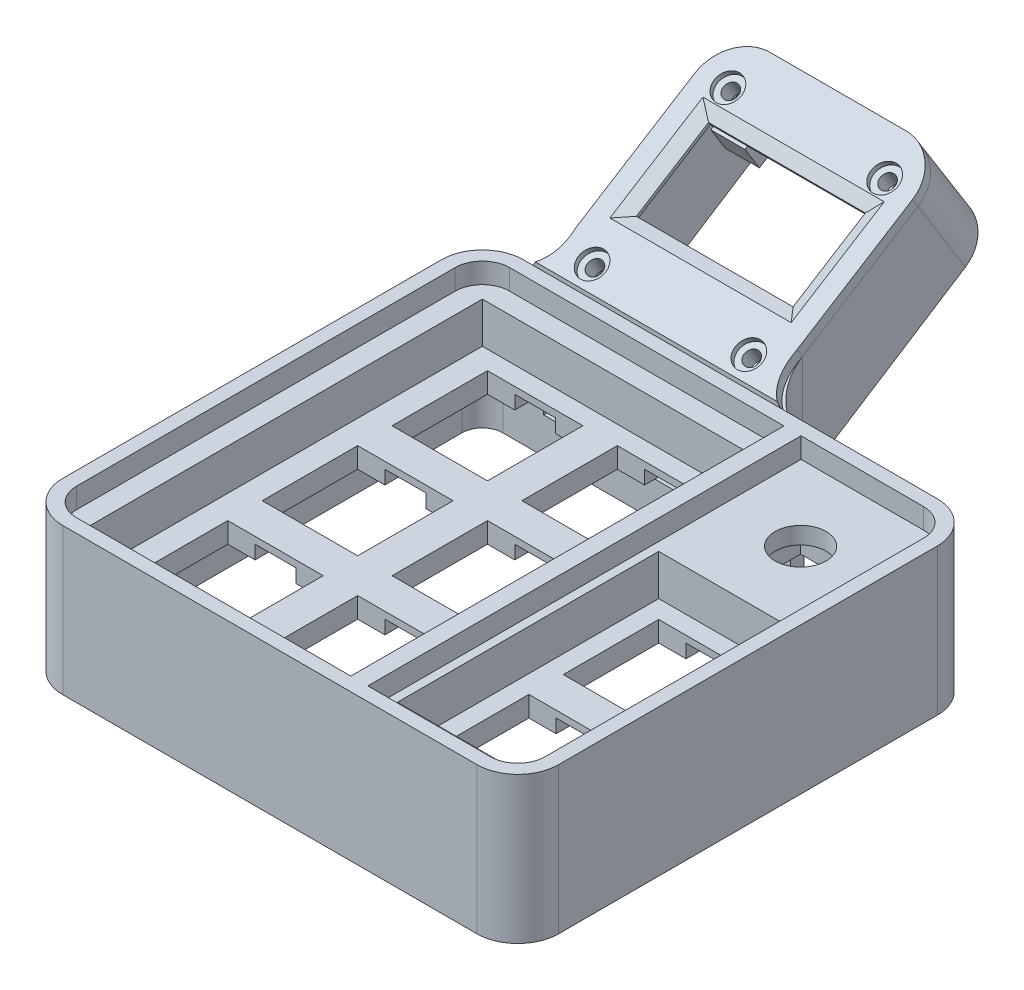
SolidWorks part; units mm, degrees
ref_plane "Ebene vorne" through (0, 0, 0) normal (0, 0, 1) x (1, 0, 0)
ref_plane "Ebene oben" through (0, 0, 0) normal (0, 1, 0) x (1, 0, 0)
ref_plane "Ebene rechts" through (0, 0, 0) normal (1, 0, 0) x (0, 0, -1)
sketch "Skizze1" plane through (0, 0, 0) normal (0, 1, 0) x (1, 0, 0)
  line L0 (-33.9289, -4.0378) -> (-33.9289, -11.968) construction
  line L1 (-59.9789, 36.498) -> (-45.9789, 36.498)
  line L2 (-59.9789, 36.498) -> (-59.9789, 22.498)
  line L3 (-59.9789, 22.498) -> (-45.9789, 22.498)
  line L4 (-45.9789, 36.498) -> (-45.9789, 22.498)
  line L5 (-40.9289, 36.498) -> (-26.9289, 36.498)
  line L6 (-40.9289, 36.498) -> (-40.9289, 22.498)
  line L7 (-40.9289, 22.498) -> (-26.9289, 22.498)
  line L8 (-26.9289, 36.498) -> (-26.9289, 22.498)
  line L9 (-59.9789, 17.448) -> (-45.9789, 17.448)
  line L10 (-59.9789, 17.448) -> (-59.9789, 3.448)
  line L11 (-59.9789, 3.448) -> (-45.9789, 3.448)
  line L12 (-45.9789, 17.448) -> (-45.9789, 3.448)
  line L13 (-40.9289, 17.448) -> (-26.9289, 17.448)
  line L14 (-40.9289, 17.448) -> (-40.9289, 3.448)
  line L15 (-40.9289, 3.448) -> (-26.9289, 3.448)
  line L16 (-26.9289, 17.448) -> (-26.9289, 3.448)
  line L17 (-15.8039, 3.448) -> (-1.8039, 3.448)
  line L18 (-15.8039, 3.448) -> (-15.8039, 17.448)
  line L19 (-15.8039, 17.448) -> (-1.8039, 17.448)
  line L20 (-1.8039, 3.448) -> (-1.8039, 17.448)
  line L21 (-59.9789, -15.602) -> (-45.9789, -15.602)
  line L22 (-59.9789, -15.602) -> (-59.9789, -1.602)
  line L23 (-59.9789, -1.602) -> (-45.9789, -1.602)
  line L24 (-45.9789, -15.602) -> (-45.9789, -1.602)
  line L25 (-40.9289, -15.602) -> (-26.9289, -15.602)
  line L26 (-40.9289, -15.602) -> (-40.9289, -1.602)
  line L27 (-40.9289, -1.602) -> (-26.9289, -1.602)
  line L28 (-26.9289, -15.602) -> (-26.9289, -1.602)
  line L29 (-15.8039, -15.602) -> (-1.8039, -15.602)
  line L30 (-15.8039, -15.602) -> (-15.8039, -1.602)
  line L31 (-15.8039, -1.602) -> (-1.8039, -1.602)
  line L32 (-1.8039, -15.602) -> (-1.8039, -1.602)
  line L33 (-68.4539, 44.223) -> (4.2961, 44.223)
  line L34 (-68.4539, 44.223) -> (-68.4539, -23.332)
  line L35 (-68.4539, -23.332) -> (4.2961, -23.332)
  line L36 (4.2961, 44.223) -> (4.2961, -23.332)
  line L37 (-8.8039, -2.5984) -> (-8.8039, -10.451) construction
  line L38 (-52.9789, -1.8609) -> (-52.9789, -10.0378) construction
  dimension "D1" = 14
  dimension "D2" = 14
  dimension "D3" = 5.05
  dimension "D4" = 5.05
  dimension "D5" = 5.05
  dimension "D6" = 11.125
  dimension "D7" = 7.725
  dimension "D8" = 8.475
  dimension "D9" = 7.73
  dimension "D10" = 6.1
extrude "Aufsatz-Linear austragen1" add sketch "Skizze1" along normal blind 3
sketch "Skizze2" plane through (0, 3, 0) normal (0, 1, 0) x (1, 0, 0)
  line L1 (-68.4539, 44.223) -> (4.2961, 44.223)
  line L2 (-68.4539, 44.223) -> (-68.4539, -23.332)
  line L3 (-68.4539, -23.332) -> (4.2961, -23.332)
  line L4 (4.2961, 44.223) -> (4.2961, -23.332)
  line L5 (-66.4539, 42.223) -> (2.2961, 42.223)
  line L6 (-66.4539, 42.223) -> (-66.4539, -21.332)
  line L7 (-66.4539, -21.332) -> (2.2961, -21.332)
  line L8 (2.2961, 42.223) -> (2.2961, -21.332)
  dimension "D1" = 2
  dimension "D2" = 2
  dimension "D3" = 2
  dimension "D4" = 2
extrude "Aufsatz-Linear austragen2" add sketch "Skizze2" along normal blind 9
sketch "Skizze3" plane through (0, 3, 0) normal (0, 1, 0) x (1, 0, 0)
  line L0 (2.2961, 42.223) -> (-66.4539, 42.223) construction
  line L1 (-22.2039, 42.223) -> (-19.7039, 42.223)
  line L2 (-22.2039, 42.223) -> (-22.2039, -21.332)
  line L3 (-22.2039, -21.332) -> (-19.7039, -21.332)
  line L4 (-19.7039, 42.223) -> (-19.7039, -21.332)
  line L5 (-66.4539, -21.332) -> (2.2961, -21.332) construction
  line L6 (4.2961, -23.332) -> (4.2961, 44.223) construction
  dimension "D1" = 2.5
  dimension "D2" = 24
extrude "Aufsatz-Linear austragen3" add sketch "Skizze3" along normal up to surface (9 mm away) up to face at (-32.0789, 12, -10.4455)
sketch "Skizze4" plane through (0, 3, 0) normal (0, 1, 0) x (1, 0, 0)
  line L0 (-22.2039, 42.223) -> (-22.2039, -21.332) construction
  line L1 (-63.4539, 39.223) -> (-23.4539, 39.223)
  line L2 (-63.4539, 39.223) -> (-63.4539, -18.332)
  line L3 (-63.4539, -18.332) -> (-23.4539, -18.332)
  line L4 (-23.4539, 39.223) -> (-23.4539, -18.332)
  line L5 (-68.4539, -23.332) -> (4.2961, -23.332) construction
  line L6 (-68.4539, 44.223) -> (-68.4539, -23.332) construction
  line L7 (4.2961, 44.223) -> (-68.4539, 44.223) construction
  line L9 (-66.4539, 42.223) -> (-22.2039, 42.223)
  line L10 (-66.4539, 42.223) -> (-66.4539, -21.332)
  line L11 (-66.4539, -21.332) -> (-22.2039, -21.332)
  line L12 (-22.2039, 42.223) -> (-22.2039, -21.332)
  dimension "D1" = 1.25
  dimension "D2" = 5
  dimension "D3" = 5
  dimension "D4" = 5
extrude "Aufsatz-Linear austragen4" add sketch "Skizze4" along normal offset from surface (6 mm away) 3 up to face at (-8.7039, 12, -10.4455)
sketch "Skizze5" plane through (0, 3, 0) normal (0, 1, 0) x (1, 0, 0)
  line L0 (-1.8039, 17.448) -> (-15.8039, 17.448) construction
  line L1 (-18.4539, 20.098) -> (0.8461, 20.098)
  line L2 (-18.4539, 20.098) -> (-18.4539, -18.252)
  line L3 (-18.4539, -18.252) -> (0.8461, -18.252)
  line L4 (0.8461, 20.098) -> (0.8461, -18.252)
  line L5 (-1.8039, 3.448) -> (-1.8039, 17.448) construction
  line L6 (-15.8039, -15.602) -> (-1.8039, -15.602) construction
  line L7 (-15.8039, -1.602) -> (-15.8039, -15.602) construction
  line L9 (-19.7039, 42.223) -> (2.2961, 42.223)
  line L10 (-19.7039, 42.223) -> (-19.7039, -21.332)
  line L11 (-19.7039, -21.332) -> (2.2961, -21.332)
  line L12 (2.2961, 42.223) -> (2.2961, -21.332)
  dimension "D1" = 2.65
  dimension "D2" = 2.65
  dimension "D3" = 2.65
  dimension "D4" = 2.65
extrude "Aufsatz-Linear austragen5" add sketch "Skizze5" along normal offset from surface (6 mm away) 3 up to face at (-8.7039, 12, -10.4455)
sketch "Skizze6" plane through (0, 9, 0) normal (0, 1, 0) x (1, 0, 0)
  line L1 (-8.7039, 37.1976) -> (-8.7039, 23.8687) construction
  line L2 (-19.7039, -21.332) -> (-19.7039, 42.223) construction
  line L3 (2.2961, -21.332) -> (2.2961, 42.223) construction
  line L4 (-14.7078, 31.1605) -> (-1.2358, 31.1605) construction
  line L5 (2.2961, 42.223) -> (-19.7039, 42.223) construction
  line L6 (0.8461, 20.098) -> (-18.4539, 20.098) construction
  circle A0 centre (-8.7039, 31.1605) radius 3.75
  dimension "D1" = 7.5
extrude "Schnitt-Linear austragen1" cut sketch "Skizze6" against normal through all
sketch "Skizze7" plane through (0, 0, 0) normal (0, -1, 0) x (1, 0, 0)
  line L0 (-8.7039, -31.1605) -> (-8.7039, -37.2605) construction
  line L1 (-16.7039, -23.1605) -> (-0.7039, -23.1605)
  line L2 (-16.7039, -23.1605) -> (-16.7039, -39.1605)
  line L3 (-16.7039, -39.1605) -> (-0.7039, -39.1605)
  line L4 (-0.7039, -23.1605) -> (-0.7039, -39.1605)
  line L5 (-11.6454, -31.1605) -> (-3.5978, -31.1605) construction
  dimension "D1" = 16
  dimension "D2" = 16
extrude "Schnitt-Linear austragen2" cut sketch "Skizze7" against normal offset from surface (6.5 mm away) 2.5 up to face at (-8.7039, 9, -27.4105)
sketch "Skizze8" plane through (0, 0, 0) normal (0, -1, 0) x (1, 0, 0)
  line L1 (-68.4539, 23.332) -> (4.2961, 23.332)
  line L2 (-68.4539, 23.332) -> (-68.4539, -44.223)
  line L3 (-68.4539, -44.223) -> (4.2961, -44.223)
  line L4 (4.2961, 23.332) -> (4.2961, -44.223)
  line L5 (2.2961, -42.223) -> (-66.4539, -42.223)
  line L6 (2.2961, -42.223) -> (2.2961, 21.332)
  line L7 (2.2961, 21.332) -> (-66.4539, 21.332)
  line L8 (-66.4539, -42.223) -> (-66.4539, 21.332)
  dimension "D1" = 2
  dimension "D2" = 2
  dimension "D3" = 2
  dimension "D4" = 2
extrude "Aufsatz-Linear austragen6" add sketch "Skizze8" along normal blind 9.5
sketch "Skizze14" plane through (0, 0, 0) normal (0, -1, 0) x (1, 0, 0)
  line L0 (-52.9789, 16.4952) -> (-52.9789, -37.7006) construction
  line L1 (-55.9789, 17.602) -> (-49.9789, 17.602)
  line L2 (-55.9789, 17.602) -> (-55.9789, -38.498)
  line L3 (-55.9789, -38.498) -> (-49.9789, -38.498)
  line L4 (-49.9789, 17.602) -> (-49.9789, -38.498)
  line L5 (-36.9289, -38.498) -> (-30.9289, -38.498)
  line L6 (-36.9289, -38.498) -> (-36.9289, 17.602)
  line L7 (-36.9289, 17.602) -> (-30.9289, 17.602)
  line L8 (-30.9289, -38.498) -> (-30.9289, 17.602)
  line L9 (-11.8039, 17.602) -> (-5.8039, 17.602)
  line L10 (-11.8039, 17.602) -> (-11.8039, -19.448)
  line L11 (-11.8039, -19.448) -> (-5.8039, -19.448)
  line L12 (-5.8039, 17.602) -> (-5.8039, -19.448)
  line L13 (-33.9289, -37.009) -> (-33.9289, 19.1358) construction
  line L14 (-8.8039, 20.7076) -> (-8.8039, -19.4677) construction
  line L15 (-59.9789, 1.602) -> (-59.9789, 15.602) construction
  line L16 (-45.9789, 15.602) -> (-45.9789, 1.602) construction
  line L17 (-40.9289, 1.602) -> (-40.9289, 15.602) construction
  line L18 (-26.9289, 15.602) -> (-26.9289, 1.602) construction
  line L19 (-15.8039, 1.602) -> (-15.8039, 15.602) construction
  line L20 (-1.8039, 15.602) -> (-1.8039, 1.602) construction
  line L21 (-59.9789, 15.602) -> (-45.9789, 15.602) construction
  line L22 (-45.9789, -36.498) -> (-59.9789, -36.498) construction
  line L23 (-1.8039, -17.448) -> (-15.8039, -17.448) construction
  dimension "D1" = 6
  dimension "D2" = 2
  dimension "D3" = 2
  dimension "D4" = 2
extrude "Schnitt-Linear austragen8" cut sketch "Skizze14" against normal blind 2
fillet "Verrundung1" radius 6 4 edges at (4.2961, 1.25, -44.223) (4.2961, 1.25, 23.332) (-68.4539, 1.25, 23.332) (-68.4539, 1.25, -44.223)
sketch "Skizze17" plane through (0, 12, 0) normal (0, 1, 0) x (1, 0, 0)
  line L8 (-62.4539, -21.332) -> (-1.7039, -21.332)
  line L9 (2.2961, -17.332) -> (2.2961, 38.223)
  line L10 (-1.7039, 42.223) -> (-62.4539, 42.223)
  line L11 (-66.4539, 38.223) -> (-66.4539, -17.332)
  line L12 (-62.4539, -21.332) -> (-1.7039, -21.332)
  line L13 (2.2961, -17.332) -> (2.2961, 38.223)
  line L14 (-1.7039, 42.223) -> (-62.4539, 42.223)
  line L15 (-66.4539, 38.223) -> (-66.4539, -17.332)
  line L20 (-62.4539, -23.332) -> (-1.7039, -23.332)
  line L21 (4.2961, -17.332) -> (4.2961, 38.223)
  line L22 (-1.7039, 44.223) -> (-62.4539, 44.223)
  line L23 (-68.4539, 38.223) -> (-68.4539, -17.332)
  line L24 (-62.4539, -23.332) -> (-1.7039, -23.332)
  line L25 (4.2961, -17.332) -> (4.2961, 38.223)
  line L26 (-1.7039, 44.223) -> (-62.4539, 44.223)
  line L27 (-68.4539, 38.223) -> (-68.4539, -17.332)
  arc A4 (-62.4539, 42.223) -> (-66.4539, 38.223) centre (-62.4539, 38.223) ccw
  arc A5 (-62.4539, 42.223) -> (-66.4539, 38.223) centre (-62.4539, 38.223) ccw
  arc A6 (-62.4539, 44.223) -> (-68.4539, 38.223) centre (-62.4539, 38.223) ccw
  arc A7 (-62.4539, 44.223) -> (-68.4539, 38.223) centre (-62.4539, 38.223) ccw
  arc A16 (-1.7039, -21.332) -> (2.2961, -17.332) centre (-1.7039, -17.332) ccw
  arc A17 (-1.7039, -21.332) -> (2.2961, -17.332) centre (-1.7039, -17.332) ccw
  arc A18 (2.2961, 38.223) -> (-1.7039, 42.223) centre (-1.7039, 38.223) ccw
  arc A19 (2.2961, 38.223) -> (-1.7039, 42.223) centre (-1.7039, 38.223) ccw
  arc A22 (-66.4539, -17.332) -> (-62.4539, -21.332) centre (-62.4539, -17.332) ccw
  arc A23 (-66.4539, -17.332) -> (-62.4539, -21.332) centre (-62.4539, -17.332) ccw
  arc A28 (-1.7039, -23.332) -> (4.2961, -17.332) centre (-1.7039, -17.332) ccw
  arc A29 (-1.7039, -23.332) -> (4.2961, -17.332) centre (-1.7039, -17.332) ccw
  arc A30 (4.2961, 38.223) -> (-1.7039, 44.223) centre (-1.7039, 38.223) ccw
  arc A31 (4.2961, 38.223) -> (-1.7039, 44.223) centre (-1.7039, 38.223) ccw
  arc A34 (-68.4539, -17.332) -> (-62.4539, -23.332) centre (-62.4539, -17.332) ccw
  arc A35 (-68.4539, -17.332) -> (-62.4539, -23.332) centre (-62.4539, -17.332) ccw
  dimension "D1" = 2
  dimension "D2" = 0
extrude "Aufsatz-Linear austragen8" add sketch "Skizze17" against normal up to surface (12 mm away) up to face at (-32.0789, 0, -10.4455)
ref_plane "Ebene1" through (-43.4539, 0, 0) normal (-1, 0, 0) x (0, 0, 1)
sketch "Skizze21" plane through (-43.4539, 0, 0) normal (-1, 0, 0) x (0, 0, 1)
  line L5 (-72.2086, 27.9873) -> (-44.223, 10.5)
  line L6 (-38.223, 12) -> (-44.223, 12) construction
  line L7 (-72.2086, 27.9873) -> (-79.1551, 16.8707)
  line L8 (-79.1551, 16.8707) -> (-44.223, -5.5)
  line L9 (-44.223, -9.5) -> (-44.223, 12) construction
  line L10 (-44.223, 10.5) -> (-44.223, -5.5)
  dimension "D1" = 122
  dimension "D2" = 1.5
  dimension "D3" = 33
  dimension "D4" = 90
  dimension "D5" = 16
extrude "Aufsatz-Linear austragen10" add sketch "Skizze21" along normal mid plane 32
sketch "Skizze25" plane through (-43.4539, 0, 0) normal (-1, 0, 0) x (0, 0, 1)
  line L22 (-70.1083, 27.5744) -> (-46.223, 22.7963)
  line L23 (-46.223, -7.3068) -> (-84.1839, 5.0487)
  line L26 (-76.4108, 17.4882) -> (-46.223, -1.8442)
  line L27 (-46.223, 9.3914) -> (-71.5724, 25.2314)
  line L28 (-46.223, -1.8442) -> (-46.223, 9.3914)
  line L29 (-71.5724, 25.2314) -> (-76.4108, 17.4882)
  line L32 (-46.223, -7.3068) -> (-46.223, 22.7963)
  line L33 (-70.1083, 27.5744) -> (-84.1839, 5.0487)
  dimension "D1" = 2
extrude "Schnitt-Linear austragen11" cut sketch "Skizze25" against normal mid plane 28
fillet "Verrundung3" radius 6 4 edges at (-27.4539, 2.5, -44.223) (-27.4539, 22.429, -75.6818) (-59.4539, 22.429, -75.6818) (-59.4539, 2.5, -44.223)
sketch "Skizze26" plane through (0, 0, -46.223) normal (0, 0, -1) x (-1, 0, 0)
  line L0 (57.4539, -4.2192) -> (57.4539, 11.7497) construction
  line L1 (29.4539, -4.2192) -> (57.4539, -4.2192)
  line L2 (29.4539, -4.2192) -> (29.4539, 0)
  line L3 (29.4539, 0) -> (57.4539, 0)
  line L4 (57.4539, -4.2192) -> (57.4539, 0)
  line L5 (66.4539, 0) -> (-2.2961, 0) construction
extrude "Schnitt-Linear austragen12" cut sketch "Skizze26" against normal up to vertex (4 mm away) up to point (-66.4539, 0, -42.223)
fillet "Verrundung4" radius 3 4 edges at (-66.4539, -4.75, 21.332) (-66.4539, -4.75, -42.223) (2.2961, -4.75, -42.223) (2.2961, -4.75, 21.332)
sketch "Skizze28" plane through (0, -9.5, 0) normal (0, -1, 0) x (1, 0, 0)
  line L0 (-57.4539, -46.223) -> (-57.4539, -77.4707) construction
  line L1 (-57.4539, -46.8175) -> (-30.4539, -46.8175)
  line L2 (-57.4539, -46.8175) -> (-57.4539, -44.223)
  line L3 (-57.4539, -44.223) -> (-30.4539, -44.223)
  line L4 (-30.4539, -46.8175) -> (-30.4539, -44.223)
  line L5 (-62.4539, -44.223) -> (-21.4539, -44.223) construction
extrude "Schnitt-Linear austragen13" cut sketch "Skizze28" against normal up to surface (9.5 mm away) up to face at (-35.8706, 0, -21.7047)
sketch "Skizze29" plane through (0, -12.3222, -7.6998) normal (0, 0.848, 0.5299) x (1, 0, 0)
  line L0 (-54.9539, 70.5674) -> (-54.9539, 74.0674) construction
  line L1 (-57.4539, 74.0674) -> (-29.4539, 74.0674) construction
  line L2 (-54.9539, 70.5674) -> (-57.4539, 70.5674) construction
  line L3 (-57.4539, 74.0674) -> (-57.4539, 45.4258) construction
  circle A0 centre (-54.9539, 70.5674) radius 1.1
  circle A1 centre (-31.9539, 70.5674) radius 1.1
  circle A2 centre (-54.9539, 47.0674) radius 1.1
  circle A3 centre (-31.9539, 47.0674) radius 1.1
  dimension "D1" = 2.2
  dimension "D4" = 3.5
  dimension "D5" = 2.5
  dimension "D2" = 23
  dimension "D3" = 23.5
ref_plane "Ebene2" through (0, -15.7992, -9.8725) normal (0, 0.848, 0.5299) x (1, 0, 0)
sketch "Skizze30" plane through (0, -15.7992, -9.8725) normal (0, 0.848, 0.5299) x (1, 0, 0)
  line L17 (-57.4539, 74.0674) -> (-52.4539, 74.0674)
  line L18 (-57.4539, 74.0674) -> (-57.4539, 67.0674)
  line L19 (-57.4539, 67.0674) -> (-52.4539, 67.0674)
  line L20 (-52.4539, 74.0674) -> (-52.4539, 67.0674)
  line L21 (-29.4539, 74.0674) -> (-34.4539, 74.0674)
  line L22 (-29.4539, 74.0674) -> (-29.4539, 67.0674)
  line L23 (-29.4539, 67.0674) -> (-34.4539, 67.0674)
  line L24 (-34.4539, 74.0674) -> (-34.4539, 67.0674)
  line L25 (-29.4539, 45.4258) -> (-34.4539, 45.4258)
  line L26 (-29.4539, 45.4258) -> (-29.4539, 52.4258)
  line L27 (-29.4539, 52.4258) -> (-34.4539, 52.4258)
  line L28 (-34.4539, 45.4258) -> (-34.4539, 52.4258)
  line L29 (-57.4539, 45.4258) -> (-52.4539, 45.4258)
  line L30 (-57.4539, 45.4258) -> (-57.4539, 52.4258)
  line L31 (-57.4539, 52.4258) -> (-52.4539, 52.4258)
  line L32 (-52.4539, 45.4258) -> (-52.4539, 52.4258)
  dimension "D1" = 5
  dimension "D2" = 7
extrude "Aufsatz-Linear austragen11" add sketch "Skizze30" against normal blind 4
extrude "Schnitt-Linear austragen14" cut sketch "Skizze29" against normal up to surface and the other way through all up to face at (-42.9042, 3.5372, -58.3346)
sketch "Skizze32" plane through (0, -12.3222, -7.6998) normal (0, 0.848, 0.5299) x (1, 0, 0)
  line L8 (-27.4539, 50.1425) -> (-27.4539, 70.0674)
  line L9 (-33.4539, 76.0674) -> (-53.4539, 76.0674)
  line L10 (-59.4539, 70.0674) -> (-59.4539, 49.6932)
  line L11 (-62.4539, 43.0674) -> (-21.4539, 43.0674)
  line L12 (-27.4539, 50.1425) -> (-27.4539, 70.0674)
  line L13 (-33.4539, 76.0674) -> (-53.4539, 76.0674)
  line L14 (-59.4539, 70.0674) -> (-59.4539, 49.6932)
  line L15 (-62.3149, 43.0674) -> (-22.9668, 43.0674)
  arc A4 (-27.4539, 70.0674) -> (-33.4539, 76.0674) centre (-33.4539, 70.0674) ccw
  arc A5 (-53.4539, 76.0674) -> (-59.4539, 70.0674) centre (-53.4539, 70.0674) ccw
  arc A6 (-27.4539, 70.0674) -> (-33.4539, 76.0674) centre (-33.4539, 70.0674) ccw
  arc A7 (-53.4539, 76.0674) -> (-59.4539, 70.0674) centre (-53.4539, 70.0674) ccw
  ellipse E6 centre (-65.4539, 49.6932) end of major axis (-65.4539, 42.6181) minor radius 6 (-63.9539, 42.8427) -> (-59.4539, 49.6932) ccw
  ellipse E7 centre (-62.4539, 35.9923) end of major axis (-62.4539, 28.9173) minor radius 6 (-62.4539, 43.0674) -> (-63.9539, 42.8427) ccw
  ellipse E8 centre (-21.4539, 50.1425) end of major axis (-21.4539, 43.0674) minor radius 6 (-27.4539, 50.1425) -> (-21.4539, 43.0674) ccw
  spline S0 degree 2 poles (-27.4539, 50.1425) (-27.7441, 44.3176) (-22.9668, 43.0674) knots 0 0 0 1 1 1
  spline S1 degree 2 poles (-62.3149, 43.0674) (-58.8701, 45.2593) (-59.4539, 49.6932) knots 0 0 0 1 1 1
  point P3 (-60.9763, 44.9212)
  point P5 (-60.4411, 44.9154)
  point P7 (-60.9677, 44.5205)
  point P14 (-61.2978, 43.9262)
  point P15 (0, 0)
  point P16 (0, 0)
  point P17 (-62.4539, 43.1102)
  point P18 (-62.3149, 43.0674)
  point P21 (-60.4241, 44.8372)
  dimension "D1" = 0
extrude "Aufsatz-Linear austragen12" add sketch "Skizze32" along normal blind 1.5 separate body
sketch "Skizze34" plane through (0, -11.0502, -6.9049) normal (0, 0.848, 0.5299) x (1, 0, 0)
  line L1 (-54.9539, 66.5674) -> (-31.9539, 66.5674)
  line L2 (-54.9539, 66.5674) -> (-54.9539, 54.0674)
  line L3 (-54.9539, 54.0674) -> (-31.9539, 54.0674)
  line L4 (-31.9539, 66.5674) -> (-31.9539, 54.0674)
  line L6 (-43.4539, 74.3043) -> (-43.4539, 68.946) construction
  line L7 (-59.4539, 70.0674) -> (-59.4539, 49.6932) construction
  line L8 (-27.4539, 50.1425) -> (-27.4539, 70.0674) construction
  circle A0 centre (-54.9539, 70.5674) radius 1.1
  circle A1 centre (-31.9539, 70.5674) radius 1.1
  circle A2 centre (-54.9539, 47.0674) radius 1.1
  circle A3 centre (-31.9539, 47.0674) radius 1.1
  circle A4 centre (-54.9539, 70.5674) radius 1.1 construction
  dimension "D1" = 2.2
  dimension "D2" = 23
  dimension "D3" = 23.5
  dimension "D4" = 23
  dimension "D5" = 12.5
  dimension "D6" = 4
extrude "Schnitt-Linear austragen16" cut sketch "Skizze34" against normal through all
sketch "Skizze36" plane through (0, -11.0502, -6.9049) normal (0, 0.848, 0.5299) x (1, 0, 0)
  circle A0 centre (-54.9539, 70.5674) radius 2
  circle A1 centre (-31.9539, 70.5674) radius 2
  circle A2 centre (-31.9539, 47.0674) radius 2
  circle A3 centre (-54.9539, 47.0674) radius 2
  dimension "D1" = 4
extrude "Schnitt-Linear austragen17" cut sketch "Skizze36" against normal blind 0.8
sketch "Skizze37" plane through (0, -23.9843, -15.3597) normal (0, -0.8421, -0.5393) x (1, 0, 0)
  line L8 (-62.5188, -34.733) -> (-23.8227, -34.8536)
  line L11 (-30.4539, -34.2748) -> (-30.4539, -36.6497)
  line L12 (-30.4539, -34.2748) -> (-30.4539, -36.6497)
  line L13 (-30.4539, -36.6497) -> (-29.4539, -36.6497)
  line L14 (-30.4539, -36.6497) -> (-29.4539, -36.6497)
  line L16 (-21.4539, -34.2748) -> (-30.4539, -34.2748)
  line L17 (-29.4539, -36.6497) -> (-29.4539, -73.7559)
  line L18 (-29.4539, -73.7559) -> (-57.4539, -73.7559)
  line L19 (-57.4539, -73.7559) -> (-57.4539, -34.2748)
  line L20 (-57.4539, -34.2748) -> (-62.4539, -34.2748)
  line L21 (-59.4539, -40.9472) -> (-59.4539, -69.7557)
  line L22 (-53.4539, -75.756) -> (-33.4539, -75.756)
  line L23 (-27.4539, -69.7557) -> (-27.4539, -41.3997)
  line L29 (-59.4539, -40.9472) -> (-59.4539, -69.7557)
  line L30 (-53.4539, -75.756) -> (-33.4539, -75.756)
  line L31 (-27.4539, -69.7557) -> (-27.4539, -41.3997)
  ellipse E0 centre (-21.4539, -41.3997) end of major axis (-21.4539, -34.2748) minor radius 6 (-21.4539, -34.2748) -> (-27.4539, -41.3997) ccw construction
  ellipse E1 centre (-65.4539, -40.9472) end of major axis (-65.4539, -33.8223) minor radius 6 (-59.4539, -40.9472) -> (-63.9539, -34.0485) ccw construction
  ellipse E10 centre (-62.4539, -27.1499) end of major axis (-62.4539, -20.025) minor radius 6 (-63.9539, -34.0485) -> (-62.4539, -34.2748) ccw
  ellipse E11 centre (-65.4539, -40.9472) end of major axis (-65.4539, -33.8223) minor radius 6 (-59.4539, -40.9472) -> (-63.9539, -34.0485) ccw
  ellipse E12 centre (-53.4539, -69.7557) end of major axis (-53.4539, -75.756) minor radius 6 (-59.4539, -69.7557) -> (-53.4539, -75.756) ccw
  ellipse E13 centre (-33.4539, -69.7557) end of major axis (-33.4539, -63.7553) minor radius 6 (-33.4539, -75.756) -> (-27.4539, -69.7557) ccw
  ellipse E14 centre (-21.4539, -41.3997) end of major axis (-21.4539, -34.2748) minor radius 6 (-21.4539, -34.2748) -> (-27.4539, -41.3997) ccw
  ellipse E16 centre (-65.4539, -40.9472) end of major axis (-65.4539, -33.8223) minor radius 6 (-59.4539, -40.9472) -> (-62.5188, -34.733) ccw
  ellipse E17 centre (-53.4539, -69.7557) end of major axis (-53.4539, -75.756) minor radius 6 (-59.4539, -69.7557) -> (-53.4539, -75.756) ccw
  ellipse E18 centre (-33.4539, -69.7557) end of major axis (-33.4539, -63.7553) minor radius 6 (-33.4539, -75.756) -> (-27.4539, -69.7557) ccw
  ellipse E19 centre (-21.4539, -41.3997) end of major axis (-21.4539, -34.2748) minor radius 6 (-23.8227, -34.8536) -> (-27.4539, -41.3997) ccw
  dimension "D1" = 0
extrude "Aufsatz-Linear austragen14" [suppressed] add sketch "Skizze37" along normal blind 1.5 separate body
fillet "Verrundung5" radius 1 4 edges at (-29.4539, 17.9252, -76.1378) (-57.4539, 17.9252, -76.1378) (-29.4539, 25.189, -71.5989) (-57.4539, 25.189, -71.5989)
sketch "Skizze38" plane through (0, 0, -44.223) normal (0, 0, -1) x (-1, 0, 0)
  line L1 (2.2131, 0) -> (21.2439, 0)
  line L2 (2.2131, 0) -> (2.2131, -9.5)
  line L3 (2.2131, -9.5) -> (21.2439, -9.5)
  line L4 (21.2439, 0) -> (21.2439, -9.5)
  line L5 (29.4539, 0) -> (0.7039, 0) construction
  line L6 (62.4539, -9.5) -> (1.7039, -9.5) construction
extrude "Schnitt-Linear austragen18" cut sketch "Skizze38" against normal blind 10
sketch "Skizze40" [suppressed] plane through (-68.4539, 0, 0) normal (-1, 0, 0) x (0, 0, 1)
  line L0 (-45.4291, -6.5087) -> (-44.3385, -7.2076)
  line L1 (-44.3385, -7.2076) -> (-44.3385, -5.426)
  line L2 (-49.842, -1.8994) -> (-44.0325, -5.6221) construction
  line L3 (-44.3385, -5.426) -> (-44.6198, -5.2458)
  line L4 (-44.6198, -5.2458) -> (-45.4291, -6.5087)
  line L5 (-50.6513, -3.1624) -> (-45.4291, -6.5087) construction
  dimension "D1" = 180
extrude "Aufsatz-Linear austragen15" [suppressed] add sketch "Skizze40" against normal up to vertex from vertex up to point (-23.8585, -6.4407, -45.5352) starting at point (-62.4994, -6.5087, -45.4291)
sketch "Skizze42" [suppressed] plane through (0, -23.747, -15.7473) normal (0, 0.842, 0.5395) x (1, 0, 0)
  circle A0 centre (-53.8539, 69.2747) radius 2.25
  circle A1 centre (-33.0539, 69.2747) radius 2.25
  circle A2 centre (-53.8539, 47.7761) radius 2.25
  circle A3 centre (-33.0539, 47.7761) radius 2.25
  dimension "D1" = 4.5
extrude "Aufsatz-Linear austragen16" [suppressed] add sketch "Skizze42" along normal offset from surface (4.5915 mm away) 4.5 up to face at (-54.9539, 21.0129, -68.7842)
sketch "Skizze44" [suppressed] plane through (0, -19.3788, -12.6358) normal (0, 0.848, 0.5299) x (1, 0, 0)
  circle A0 centre (-54.9539, 70.55) radius 0.85
  circle A1 centre (-31.9539, 70.55) radius 0.85
  circle A2 centre (-31.9539, 47.05) radius 0.85
  circle A3 centre (-54.9539, 47.05) radius 0.85
  dimension "D1" = 1.7
extrude "Schnitt-Linear austragen21" [suppressed] cut sketch "Skizze44" against normal offset from surface (5.0645 mm away) 1 up to face at (-42.9689, 4.9286, -60.5074)
sketch "Skizze46" plane through (0, -12.3222, -7.6998) normal (0, -0.848, -0.5299) x (1, 0, 0)
  circle A0 centre (-31.9539, -70.5674) radius 1.1
  circle A1 centre (-54.9539, -70.5674) radius 1.1
  circle A4 centre (-31.9539, -70.5674) radius 1.1 construction
  circle A5 centre (-54.9539, -70.5674) radius 1.1 construction
  circle A6 centre (-54.9539, -47.0674) radius 1.1
  circle A7 centre (-54.9539, -47.0674) radius 2.325
  circle A9 centre (-31.9539, -70.5674) radius 2.325
  circle A10 centre (-54.9539, -70.5674) radius 2
  circle A11 centre (-31.9539, -47.0674) radius 1.1
  circle A12 centre (-31.9539, -47.0674) radius 2.325
  dimension "D1" = 2.2
extrude "Aufsatz-Linear austragen17" add sketch "Skizze46" along normal blind 1.8
sketch "Sketch1" plane through (0, -25.2509, -16.1806) normal (0, -0.842, -0.5395) x (1, 0, 0)
  line L0 (-200.4007, -546.7833) -> (-867.0674, -546.7833) construction
  line L1 (-43.3797, -51.2457) -> (-43.3797, -55.0338)
  line L2 (-43.3797, -55.0338) -> (-42.0717, -56.6703)
  line L3 (-42.0717, -56.6703) -> (-38.3626, -51.1175)
  line L4 (-37.4297, -51.7406) -> (-41.3375, -57.591)
  line L5 (-41.3375, -57.591) -> (-37.941, -61.8301)
  line L6 (-38.7762, -62.4994) -> (-43.3797, -56.6703)
  line L7 (-43.3797, -56.6703) -> (-43.3797, -62.409)
  line L8 (-43.6369, -62.6662) -> (-47.2312, -62.6662)
  line L9 (-50.137, -59.7603) -> (-50.137, -58.5653)
  line L10 (-47.094, -55.6488) -> (-44.524, -55.6488)
  line L11 (-44.524, -55.6488) -> (-44.524, -51.2457)
  line L12 (-44.524, -56.6017) -> (-44.524, -61.6263)
  line L13 (-44.524, -61.6263) -> (-46.964, -61.6263)
  line L14 (-49.0612, -59.5291) -> (-49.0612, -58.7242)
  line L15 (-47.1662, -56.6017) -> (-44.524, -56.6017)
  circle A0 centre (-43.7073, -56.7837) radius 9
  circle A1 centre (-43.7073, -56.7837) radius 10
  arc A2 (-38.3626, -51.1175) -> (-37.4297, -51.7406) centre (-37.8962, -51.429) cw
  arc A3 (-37.941, -61.8301) -> (-38.7762, -62.4994) centre (-38.3586, -62.1648) cw
  arc A4 (-43.3797, -62.409) -> (-43.6369, -62.6662) centre (-43.6369, -62.409) cw
  arc A5 (-47.2312, -62.6662) -> (-50.137, -59.7603) centre (-47.2312, -59.7603) cw
  arc A6 (-50.137, -58.5653) -> (-47.094, -55.6488) centre (-47.2179, -58.5653) cw
  arc A7 (-44.524, -51.2457) -> (-43.3797, -51.2457) centre (-43.9518, -51.2457) cw
  arc A8 (-46.964, -61.6263) -> (-49.0612, -59.5291) centre (-46.964, -59.5291) cw
  arc A9 (-49.0612, -58.7242) -> (-47.1662, -56.6017) centre (-46.9251, -58.7242) cw
  dimension "D1" = 1
  dimension "D2" = 18
extrude "Cut-Extrude1" [suppressed] cut sketch "Sketch1" against normal blind 1 contours A7 L11 L10 A6 L9 A5 L8 A4 L7 L6 A3 L5 L4 A2 L3 L2 L1 L14 A9 L15 L12 L13 A8 | A1 A0
chamfer "Chamfer1" distance 1.8 angle 30 4 edges at (-31.9539, 20.9132, -58.057) (-43.4539, 17.6012, -52.7567) (-54.9539, 20.9132, -58.057) (-43.4539, 24.2252, -63.3573) first distance on face at (-54.9539, 12.8319, -45.1242)
sketch "Skizze47" plane through (-68.4539, 0, 0) normal (-1, 0, 0) x (0, 0, 1)
  line L0 (-44.4325, 15.1488) -> (-44.4325, 8.2821)
  line L1 (-44.4325, 8.2821) -> (-42.0423, 8.9729)
  line L2 (-42.0423, 8.9729) -> (-42.1528, 13.6566)
  line L3 (-42.1528, 13.6566) -> (-44.4325, 15.1488)
  line L4 (-44.0325, 10.3809) -> (-44.0325, -5.622) construction
  dimension "D1" = 0.4
extrude "Schnitt-Linear austragen23" cut sketch "Skizze47" against normal through all
